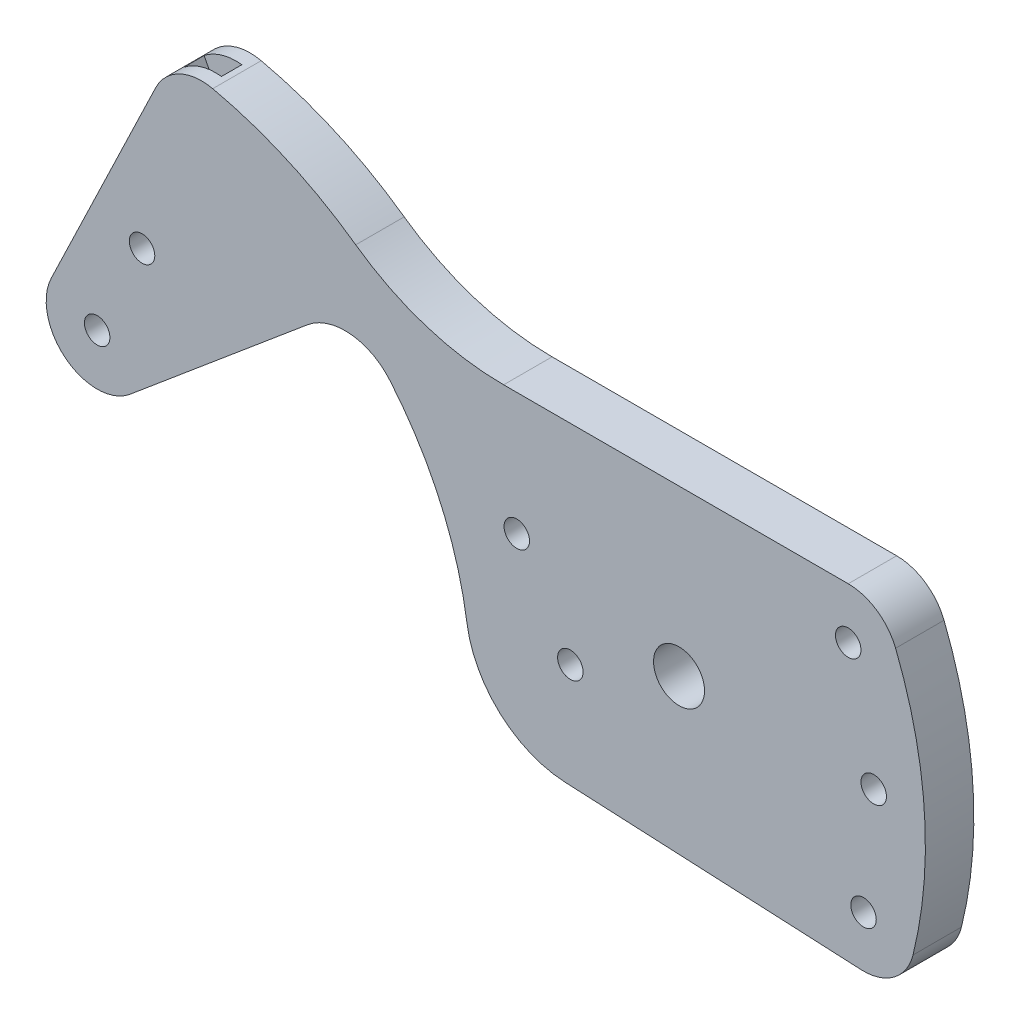
SolidWorks part; units mm, degrees
ref_plane "Front Plane" through (0, 0, 0) normal (0, 0, 1) x (1, 0, 0)
ref_plane "Top Plane" through (0, 0, 0) normal (0, 1, 0) x (1, 0, 0)
ref_plane "Right Plane" through (0, 0, 0) normal (1, 0, 0) x (0, 0, -1)
sketch "Sketch1" plane through (0, 0, 0) normal (0, 0, 1) x (1, 0, 0)
  line L1 (-5, -5) -> (5, -5) construction
  line L2 (-5, -5) -> (-5, 5) construction
  line L3 (-5, 5) -> (5, 5) construction
  line L4 (5, -5) -> (5, 5) construction
  line L5 (-5, -5) -> (5, 5) construction
  line L6 (-5, 5) -> (5, -5) construction
  line L7 (35.6989, -31.9883) -> (-22.3088, -29.1817)
  line L9 (-114.3299, 24.3337) -> (-123.1299, 6.0337)
  line L10 (-107.6899, -5.9604) -> (-72.8648, 23.2613)
  line L11 (-114.3299, 24.3337) -> (-102.6393, 48.6449)
  line L16 (-65.4725, 14.4515) -> (-108.3178, -21.5) construction
  line L17 (50.9822, -33.5) -> (-177.2181, -33.5) construction
  line L20 (-34.3975, 32.3) -> (33.1822, 32.3)
  circle A0 centre (0, 0) radius 5
  circle A1 centre (-31.8178, 8.3) radius 2.5
  circle A2 centre (-21.3178, -8.7) radius 2.5
  circle A3 centre (33.1822, 22.3) radius 2.5
  circle A4 centre (38.1822, -0.1) radius 2.5
  circle A5 centre (36.1822, -22) radius 2.5
  circle A6 centre (36.1822, -22) radius 2.5 construction
  circle A7 centre (38.1822, -0.1) radius 2.5 construction
  circle A8 centre (33.1822, 22.3) radius 2.5 construction
  circle A9 centre (-31.8178, 8.3) radius 2.5 construction
  circle A10 centre (-21.3178, -8.7) radius 2.5 construction
  arc A12 (-41.605, -11.6848) -> (-22.3088, -29.1817) centre (-21.3178, -8.7) ccw
  arc A13 (32.976, -31.8566) -> (28.2895, 32.3) centre (-34.3029, -4.5217) ccw construction
  arc A14 (45.8883, -24.4068) -> (42.4751, 25.9934) centre (-34.3029, -4.5217) ccw
  arc A15 (35.6989, -31.9883) -> (45.8883, -24.4068) centre (36.1822, -22) ccw
  arc A16 (42.4751, 25.9934) -> (33.1822, 32.3) centre (33.1822, 22.3) ccw
  circle A17 centre (-105.3178, 20) radius 2.5
  circle A18 centre (-34.3029, -4.5217) radius 82.6199 construction
  circle A19 centre (-114.1178, 1.7) radius 2.5
  circle A21 centre (-105.3178, 20) radius 2.5 construction
  circle A22 centre (-114.1178, 1.7) radius 2.5 construction
  circle A23 centre (-105.3178, 20) radius 10 construction
  arc A24 (-123.1299, 6.0337) -> (-107.6899, -5.9604) centre (-114.1178, 1.7) ccw
  arc A27 (-91.4485, 54.071) -> (-102.6393, 48.6449) centre (-93.6271, 44.3112) ccw
  circle A31 centre (-34.3029, -4.5217) radius 72.6199 construction
  arc A32 (-41.605, -11.6848) -> (-56.6627, 21.8438) centre (-108.3178, -21.5) ccw
  arc A33 (-31.0644, -26.7412) -> (-91.4485, 54.071) centre (-108.3178, -21.5) ccw
  arc A34 (-63.4016, 41.5721) -> (-34.3975, 32.3) centre (-34.3975, 82.3) ccw
  arc A35 (-56.6627, 21.8438) -> (-72.8648, 23.2613) centre (-65.4725, 14.4515) ccw
  circle A36 centre (-65.4725, 14.4515) radius 10.5004 construction
  circle A37 centre (-108.3178, -21.5) radius 67.4309 construction
  circle A38 centre (-108.3178, -21.5) radius 77.4309 construction
  circle A39 centre (-108.3178, -21.5) radius 10.5004 construction
  circle A40 centre (-108.3178, -21.5) radius 11.5004 construction
  circle A41 centre (0, 0) radius 33 construction
  point P35 (50.3427, -4.5217)
  point P37 (37.1696, 16.7103)
  point P54 (-36.0565, -0.0269)
  point P75 (-40.8381, -1.4887)
  dimension "D1" = 10
  dimension "D3" = 10
  dimension "D5" = 50
  dimension "D7" = 40
  dimension "D4" = 10
  dimension "D2" = 10
  dimension "D8" = 1
extrude "Boss-Extrude1" add sketch "Sketch1" along normal mid plane 9.5 contours A0 L4 L3 | A0 L1 L4 | A0 L2 L1 | A0 L3 L2 | A35 A32 A12 A33 A27 L11 L9 A24 L10 A17 A19 region at (6.7597, -29.2489, 0) region at (-82.3925, 21.3461, 0)
sketch "Sketch2" plane through (0, 0, 0) normal (0, 0, 1) x (1, 0, 0)
  line L0 (-93.6271, 44.3112) -> (-96.4023, 53.9184) construction
  line L1 (-78.2271, 18.7618) -> (-72.8648, 23.2613)
  line L2 (-93.6271, 44.3112) -> (-84.6823, 13.3452) construction
  line L3 (-91.6689, 44.8769) -> (-78.2271, 18.7618)
  line L4 (-94.4967, 54.2733) -> (-93.6271, 44.3112) construction
  line L5 (-93.6271, 44.3112) -> (-90.4984, 8.4649) construction
  line L6 (-98.2036, 53.2026) -> (-93.6271, 44.3112) construction
  line L7 (-93.6271, 44.3112) -> (-79.798, 17.4436) construction
  line L8 (-99.8894, 52.1076) -> (-95.5854, 43.7456)
  line L9 (-92.4867, 54.246) -> (-91.6689, 44.8769)
  line L12 (-92.369, 6.8953) -> (-78.2271, 18.7618)
  line L13 (-107.6899, -5.9604) -> (-72.8648, 23.2613) construction
  line L14 (-100.8204, 53.9163) -> (-90.7503, 34.3517) construction
  line L15 (-92.6635, 56.2725) -> (-90.7503, 34.3517) construction
  line L16 (-95.5854, 43.7456) -> (-92.369, 6.8953)
  line L18 (-96.504, 54.2707) -> (-78.2271, 18.7618) construction
  line L19 (-96.504, 54.2707) -> (-92.369, 6.8953) construction
  line L20 (-92.369, 6.8953) -> (-107.6899, -5.9604)
  line L22 (-93.6271, 44.3112) -> (-90.3766, 7.0692) construction
  line L23 (-93.6271, 44.3112) -> (-80.0054, 17.8465) construction
  arc A0 (-92.4867, 54.246) -> (-99.8894, 52.1076) centre (-93.6271, 44.3112) ccw
  arc A1 (-94.4967, 54.2733) -> (-98.2036, 53.2026) centre (-93.6271, 44.3112) ccw construction
  arc A2 (-92.6635, 56.2725) -> (-100.8204, 53.9163) centre (-93.6271, 44.3112) ccw construction
  arc A3 (-91.4485, 54.071) -> (-102.6393, 48.6449) centre (-93.6271, 44.3112) ccw construction
  point P33 (-96.4023, 53.9184)
  dimension "D3" = 7
  dimension "D4" = 20
  dimension "D1" = 2
  dimension "D2" = 2
extrude "Cut-Extrude1" cut sketch "Sketch2" against normal mid plane 4 contours A0 L8 L12 L9 region at (-89.6335, 28.8858, 0)
